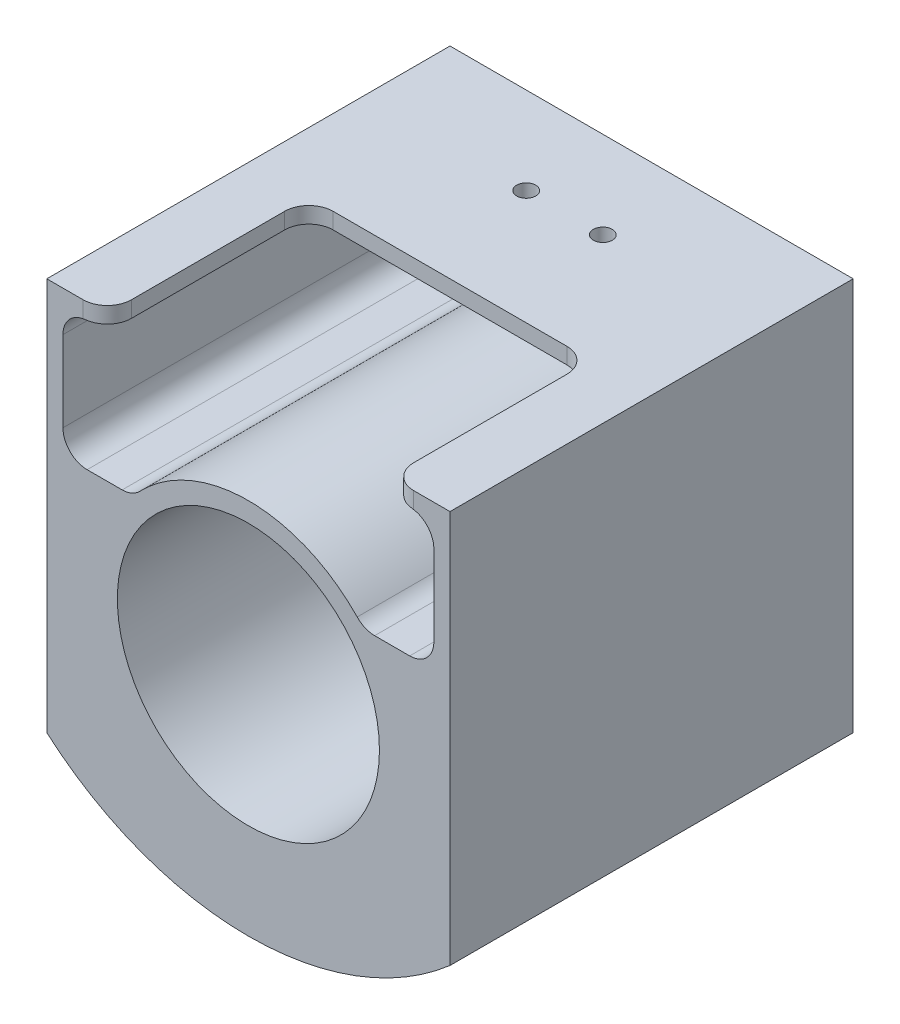
SolidWorks part; units mm, degrees
ref_plane "Front Plane" through (0, 0, 0) normal (0, 0, 1) x (1, 0, 0)
ref_plane "Top Plane" through (0, 0, 0) normal (0, 1, 0) x (1, 0, 0)
ref_plane "Right Plane" through (0, 0, 0) normal (1, 0, 0) x (0, 0, -1)
sketch "Sketch1" plane through (0, 0, 0) normal (0, 0, 1) x (1, 0, 0)
  line L1 (0, 0) -> (0, -38.1) construction
  line L2 (-25, 0) -> (-25, -28.7508)
  line L3 (25, 0) -> (25, -28.7508)
  line L4 (-25, 0) -> (-25, 20)
  line L5 (-25, 20) -> (25, 20)
  line L6 (25, 20) -> (25, 0)
  arc A0 (-25, -28.7508) -> (25, -28.7508) centre (0, 0) ccw
  dimension "D1" = 76.2
  dimension "D2" = 50
  dimension "D3" = 20
extrude "Boss-Extrude2" add sketch "Sketch1" along normal blind 50
sketch "Sketch2" plane through (0, 0, 50) normal (0, 0, 1) x (1, 0, 0)
  line L6 (0, 6.25) -> (0, -26.25) construction
  circle A0 centre (0, -10) radius 16.25
  dimension "D2" = 32.5
  dimension "D1" = 10
extrude "Cut-Extrude1" cut sketch "Sketch2" against normal through all both
sketch "Sketch4" plane through (0, 0, 50) normal (0, 0, 1) x (1, 0, 0)
  line L0 (-23, 18) -> (23, 18)
  line L3 (0, 20) -> (0, 6.25) construction
  line L4 (25, 20) -> (-25, 20) construction
  line L5 (23, 2) -> (14.3178, 2)
  line L6 (-23, 18) -> (-23, 2)
  line L7 (-23, 2) -> (-14.3178, 2)
  line L8 (-25, 20) -> (-25, -28.7508) construction
  line L9 (23, 18) -> (23, 2)
  circle A2 centre (0, -10) radius 16.25 construction
  arc A3 (14.3178, 2) -> (-14.3178, 2) centre (0, -10) ccw
  point P2 (0, 13.125)
  point P14 (0, 18)
  dimension "D1" = 37.3631
  dimension "D2" = 2
  dimension "D3" = 2
  dimension "D4" = 16
extrude "Cut-Extrude3" cut sketch "Sketch4" against normal through all
fillet "Fillet1" radius 3 6 edges at (23, 18, 25) (23, 2, 25) (14.3178, 2, 25) (-14.3178, 2, 25) (-23, 2, 25) (-23, 18, 25)
sketch "Sketch5" plane through (0, 20, 0) normal (0, 1, 0) x (1, 0, 0)
  line L0 (25, -50) -> (-25, -50) construction
  line L1 (-17.5, -50) -> (17.5, -50)
  line L2 (-17.5, -50) -> (-17.5, -25)
  line L3 (-17.5, -25) -> (17.5, -25)
  line L4 (17.5, -50) -> (17.5, -25)
  line L5 (0, 0) -> (0, -50) construction
  dimension "D1" = 35
  dimension "D2" = 25
extrude "Cut-Extrude4" cut sketch "Sketch5" against normal blind 10
fillet "Fillet2" radius 3 4 edges at (17.5, 19, 50) (17.5, 19, 25) (-17.5, 19, 25) (-17.5, 19, 50)
ref_plane "Plane1" through (0, 0, 14) normal (0, 0, 1) x (1, 0, 0)
sketch "Sketch6" plane through (0, 0, 14) normal (0, 0, 1) x (1, 0, 0)
  line L0 (0, -10) -> (0, 3) construction
  line L1 (0, -10) -> (-4.4463, 2.216) construction
  circle A1 centre (0, -10) radius 16.25 construction
  circle A3 centre (0, -10) radius 9.5
  circle A8 centre (0, -10) radius 16.1
  circle A9 centre (0, -10) radius 13 construction
  circle A10 centre (-4.4463, 2.216) radius 1.65
  circle A11 centre (12.216, -5.5537) radius 1.65
  circle A12 centre (4.4463, -22.216) radius 1.65
  circle A13 centre (-12.216, -14.4463) radius 1.65
  dimension "D1" = 19
  dimension "D6" = 13
  dimension "D7" = 32.2
  dimension "D2" = 3.5
  dimension "D3" = 3.3
  dimension "D4" = 20
  dimension "D5" = 4
extrude "Boss-Extrude3" add sketch "Sketch6" against normal blind 5
sketch "Sketch7" plane through (0, 0, 0) normal (1, 0, 0) x (0, 0, -1)
  circle A0 centre (-40, -32) radius 2.25
  circle A1 centre (-10, -32) radius 2.25
  dimension "D3" = 4.5
  dimension "D1" = 32
  dimension "D2" = 10
  dimension "D4" = 30
extrude "Cut-Extrude5" cut sketch "Sketch7" against normal through all both and the other way through all
sketch "Sketch8" plane through (0, 20, 0) normal (0, 1, 0) x (1, 0, 0)
  line L0 (0, 0) -> (0, -25) construction
  line L1 (25, 0) -> (-25, 0) construction
  line L2 (14.5, -25) -> (-14.5, -25) construction
  circle A0 centre (-4.75, -10.8) radius 1.175
  circle A1 centre (4.75, -10.8) radius 1.175
  dimension "D1" = 2.35
  dimension "D2" = 9.5
  dimension "D3" = 10.8
extrude "Cut-Extrude6" cut sketch "Sketch8" against normal up to next (2 mm away) contours A0 | A1
